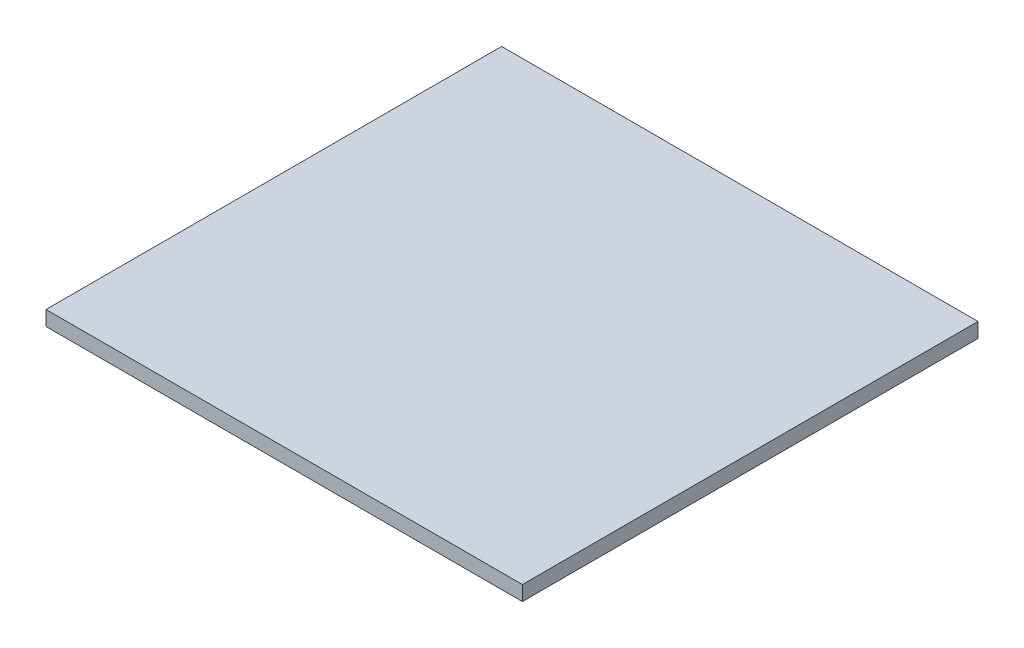
SolidWorks part; units mm, degrees
ref_plane "Front Plane" through (0, 0, 0) normal (0, 0, 1) x (1, 0, 0)
ref_plane "Top Plane" through (0, 0, 0) normal (0, 1, 0) x (1, 0, 0)
ref_plane "Right Plane" through (0, 0, 0) normal (1, 0, 0) x (0, 0, -1)
sketch "Sketch1" plane through (0, 0, 0) normal (0, 1, 0) x (1, 0, 0)
  line L1 (-44.2815, 20.698) -> (59.0185, 20.698)
  line L2 (-44.2815, 20.698) -> (-44.2815, -78.102)
  line L3 (-44.2815, -78.102) -> (59.0185, -78.102)
  line L4 (59.0185, 20.698) -> (59.0185, -78.102)
  dimension "D1" = 103.3
  dimension "D2" = 98.8
extrude "Boss-Extrude1" add sketch "Sketch1" along normal blind 3.2
equation "\"Fit\"= 1"
equation "\"cover width\"= 98.8"
equation "\"bottom 5 length\" = 103.3"
equation "\"thinner acrylic\"= 3.2"
equation "\"D1@Sketch1\"=\"bottom 5 length\""
equation "\"D2@Sketch1\"=\"cover width\""
equation "\"D1@Boss-Extrude1\"=\"thinner acrylic\""
